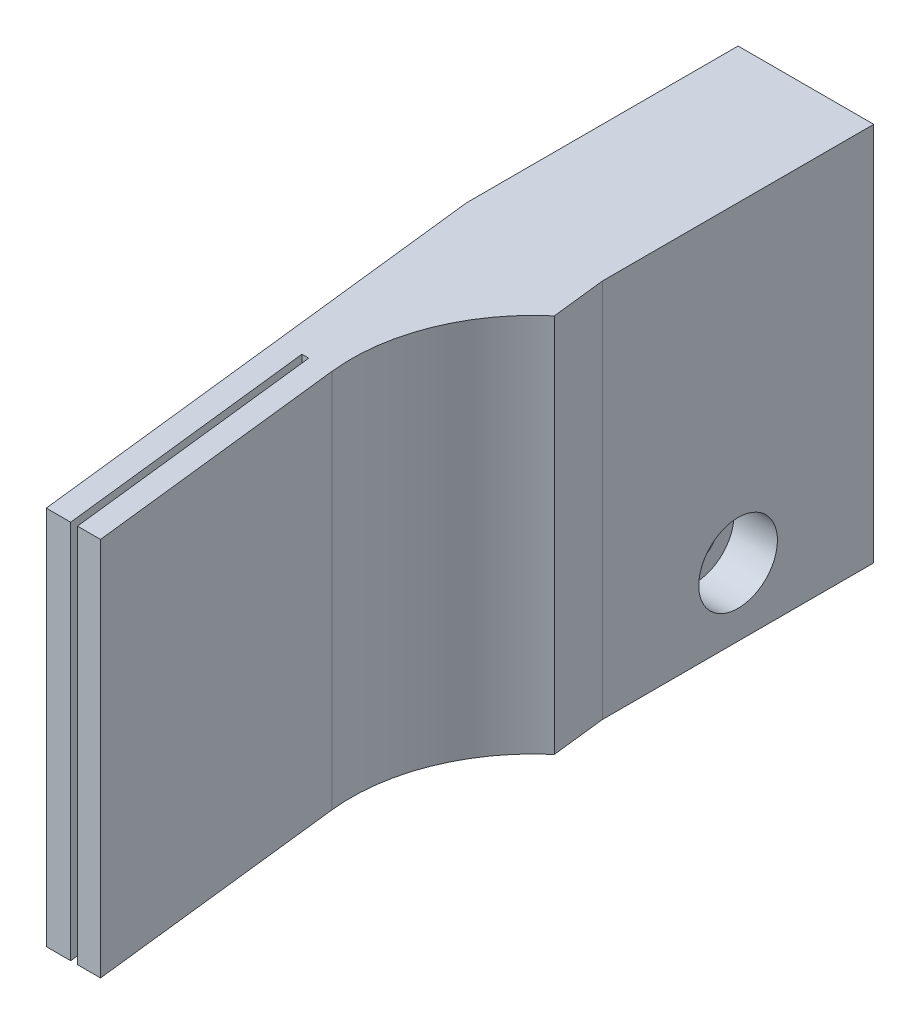
SolidWorks part; units mm, degrees
ref_plane "Front Plane" through (0, 0, 0) normal (0, 0, 1) x (1, 0, 0)
ref_plane "Top Plane" through (0, 0, 0) normal (0, 1, 0) x (1, 0, 0)
ref_plane "Right Plane" through (0, 0, 0) normal (1, 0, 0) x (0, 0, -1)
sketch "Profile" plane through (0, 0, 0) normal (0, 0, 1) x (1, 0, 0)
  line L1 (-6.35, 22.86) -> (6.35, 22.86)
  line L2 (-6.35, 22.86) -> (-6.35, 0)
  line L3 (-6.35, 0) -> (6.35, 0)
  line L4 (6.35, 22.86) -> (6.35, 0)
  line L5 (0, 0) -> (6.35, 0)
  line L6 (0, 0) -> (0, -12.7)
  line L7 (0, -12.7) -> (6.35, -12.7)
  line L8 (6.35, 0) -> (6.35, -12.7)
  dimension "D1" = 22.86
  dimension "D2" = 12.7
  dimension "D3" = 6.35
  dimension "D4" = 12.7
extrude "Boss-Extrude1" add sketch "Profile" along normal mid plane 25.4 contours L4 L1 L2 L3 | L8 L3 L6 L7 region at (0, 11.43, 0) region at (3.175, -6.35, 0)
sketch "ScrewHole" plane through (0, 0, 0) normal (-1, 0, 0) x (0, 0, 1)
  line L0 (12.7, 0) -> (12.7, -12.7) construction
  line L1 (12.7, -12.7) -> (-12.7, -12.7) construction
  circle A0 centre (0, -6.35) radius 2.159
  point P5 (12.7, -6.35)
  point P10 (0, -12.7)
  dimension "D1" = 4.318
extrude "Cut-Extrude1" cut sketch "ScrewHole" against normal through all both
sketch "Sketch3" plane through (6.35, 0, 0) normal (1, 0, 0) x (0, 0, -1)
  circle A0 centre (0, -6.35) radius 2.159 construction
  circle A1 centre (0, -6.35) radius 2.159
  circle A2 centre (0, -6.35) radius 3.683
  dimension "D1" = 7.366
extrude "Cut-Extrude2" cut sketch "Sketch3" against normal blind 4.064
sketch "Sketch4" plane through (0, 0, 12.7) normal (0, 0, 1) x (1, 0, 0)
  line L0 (-6.35, 22.86) -> (-6.35, 0) construction
  line L1 (-1.4478, 20.955) -> (-3.175, 20.955)
  line L2 (-1.4478, 20.955) -> (-1.4478, 1.905)
  line L3 (-1.4478, 1.905) -> (-3.175, 1.905)
  line L4 (-3.175, 20.955) -> (-3.175, 1.905)
  line L5 (-3.175, 18.415) -> (-6.35, 18.415)
  line L6 (-3.175, 18.415) -> (-3.175, 4.445)
  line L7 (-3.175, 4.445) -> (-6.35, 4.445)
  line L8 (-6.35, 18.415) -> (-6.35, 4.445)
  point P10 (-6.35, 11.43)
  point P11 (-6.35, 11.43)
  point P12 (-3.175, 11.43)
  line M10 (-6.35, 22.86) -> (-6.35, 0)
  dimension "D1" = 13.97
  dimension "D2" = 1.7272
  dimension "D3" = 19.05
  dimension "D4" = 3.175
extrude "Cut-Extrude3" cut sketch "Sketch4" against normal through all both and the other way through all contours L7 L4 L5 M10 | L1 L4 L3 L2 region at (-2.3114, 11.43, 12.7) region at (-4.7625, 11.43, 12.7)
sketch "Sketch5" plane through (0, -12.7, 0) normal (0, -1, 0) x (1, 0, 0)
  line L0 (-6.35, 12.7) -> (-1.27, 57.15)
  line L1 (6.35, 12.7) -> (11.43, 57.15)
  line L2 (-6.35, 12.7) -> (0, 12.7) construction
  line L3 (-1.27, 57.15) -> (11.43, 57.15)
  line L4 (-6.35, 12.7) -> (6.35, 12.7)
  line L5 (3.81, 57.15) -> (1.0165, 32.7066)
  line L6 (1.016, 57.15) -> (-1.7775, 32.7066)
  line L7 (1.6551, 57.15) -> (-1.1384, 32.7066)
  line L8 (-1.7775, 32.7066) -> (-1.1384, 32.7066)
  arc A0 (1.0165, 32.7066) -> (6.9306, 17.78) centre (17.9313, 30.7735) ccw
  point P16 (0, 0)
  line M5 (6.35, 12.7) -> (0, 12.7)
  dimension "D5" = 17.0249
  dimension "D1" = 5.08
  dimension "D2" = 44.45
  dimension "D3" = 5.08
  dimension "D4" = 5.08
  dimension "D6" = 0.635
  dimension "D7" = 2.286
other "AlignGroup1"
extrude "Boss-Extrude2" add sketch "Sketch5" against normal up to surface (35.56 mm away) contours A0 L5 L3 L0 L4 L1 M5 region at (-0.3835, -12.7, 30.0201) up to face at (0, 22.86, 0)
